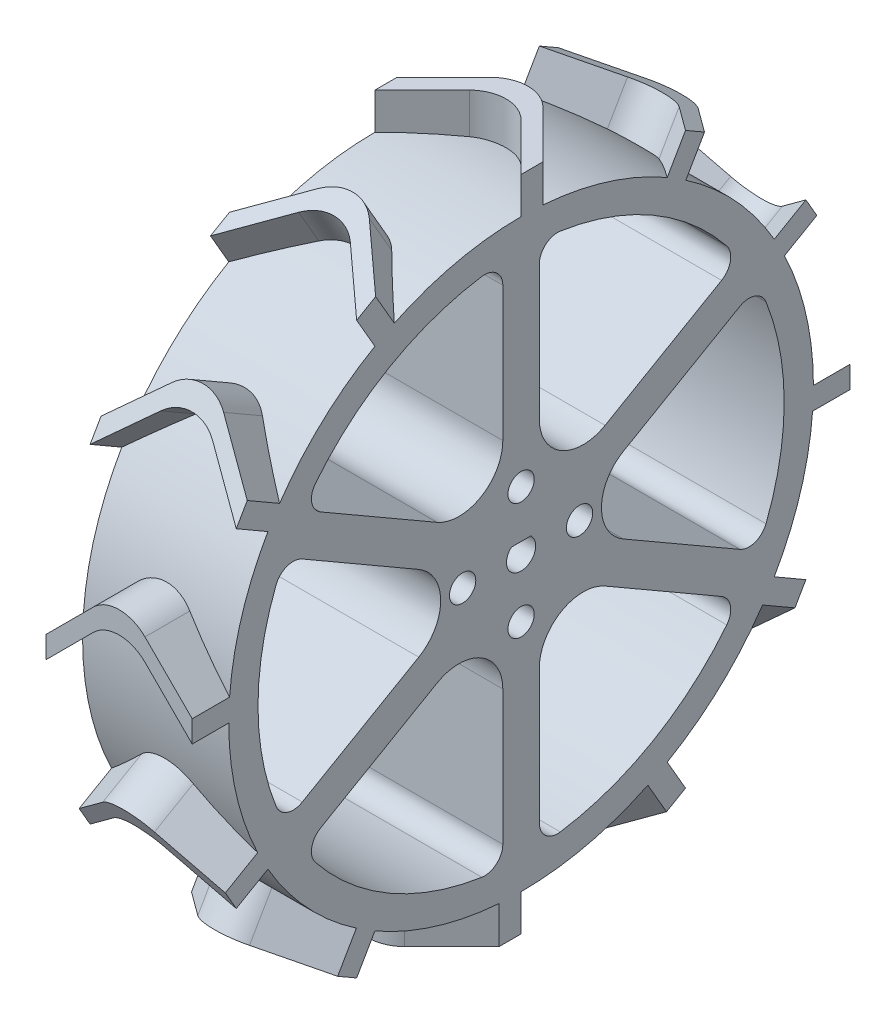
SolidWorks part; units mm, degrees
material "PLA 15%"
ref_plane "Front Plane" through (0, 0, 0) normal (0, 0, 1) x (1, 0, 0)
ref_plane "Top Plane" through (0, 0, 0) normal (0, 1, 0) x (1, 0, 0)
ref_plane "Right Plane" through (0, 0, 0) normal (1, 0, 0) x (0, 0, -1)
sketch "Sketch2" plane through (0, 0, 0) normal (1, 0, 0) x (0, 0, -1)
  circle A2 centre (0, 0) radius 40
  dimension "D1" = 80
extrude "Boss-Extrude1" add sketch "Sketch2" along normal blind 20
sketch "Sketch4" plane through (0, 0, 0) normal (0, 1, 0) x (1, 0, 0)
  line L8 (0, 0) -> (20, 0) construction
  line L9 (20, -40) -> (20, 40) construction
  line L10 (0, 0) -> (6.4645, 6.4645)
  line L11 (13.5355, 6.4645) -> (20, 0)
  line L12 (20, 0) -> (20, 3)
  line L13 (20, 3) -> (13.5355, 9.4645)
  line L14 (6.4645, 9.4645) -> (0, 3)
  line L15 (0, 40) -> (0, -40) construction
  line L16 (0, 3) -> (0, 0)
  arc A0 (13.5355, 9.4645) -> (6.4645, 9.4645) centre (10, 5.9289) ccw
  arc A1 (6.4645, 6.4645) -> (13.5355, 6.4645) centre (10, 2.9289) cw
  point P4 (10, 0)
  point P18 (10, 13)
  point P21 (10, 10)
  dimension "D3" = 5
  dimension "D1" = 3
  dimension "D2" = 3
  dimension "D4" = 10
extrude "Boss-Extrude2" add sketch "Sketch4" along normal blind 45
pattern_circular "CirPattern2" count 12 over 360 about axis through (20, 0, 0) along (-1, 0, 0) of "Boss-Extrude2"
sketch "Sketch5" plane through (0, 0, 0) normal (-1, 0, 0) x (0, 0, 1)
  line L0 (0, 0) -> (0, 40) construction
  line L1 (0, 0) -> (34.641, 20) construction
  line L6 (2.5, 33.1248) -> (2.5, 4.3301)
  line L8 (27.4369, 18.7274) -> (2.5, 4.3301)
  circle A0 centre (0, 0) radius 40 construction
  arc A2 (5.3731, 35.5968) -> (28.1411, 22.4517) centre (0, 0) cw
  arc A6 (28.1411, 22.4517) -> (27.4369, 18.7274) centre (26.1869, 20.8925) cw
  arc A7 (5.3731, 35.5968) -> (2.5, 33.1248) centre (5, 33.1248) ccw
  circle A10 centre (0, 0) radius 40 construction
  point P11 (0, 35.9131)
  point P22 (2.5, 35.9131)
  dimension "D1" = 2.5
  dimension "D2" = 4
  dimension "D8" = 2.5
  dimension "D7" = 2.5
  dimension "D9" = 60
extrude "Cut-Extrude3" cut sketch "Sketch5" against normal up to next
fillet "Fillet1" radius 6 1 edges at (10, 4.3301, 2.5)
pattern_circular "CirPattern3" count 6 over 360 about axis through (0, 0, 0) along (1, 0, 0) of "Cut-Extrude3", "Fillet1"
sketch "Sketch6" plane through (0, 0, 0) normal (-1, 0, 0) x (0, 0, 1)
  circle A0 centre (0, 8) radius 1.8
  circle A1 centre (8, 0) radius 1.8
  circle A2 centre (0, -8) radius 1.8
  circle A3 centre (-8, 0) radius 1.8
  point P0 (0, 0)
  point P13 (0, 0)
  dimension "D1" = 3.6
  dimension "D2" = 8
  dimension "D3" = 4
extrude "Cut-Extrude4" cut sketch "Sketch6" against normal up to next
sketch "Sketch8" plane through (0, 0, 0) normal (1, 0, 0) x (0, 0, -1)
  line L0 (1.3229, 1.5) -> (-1.3229, 1.5)
  arc A0 (1.3229, 1.5) -> (-1.3229, 1.5) centre (0, 0) cw
  point P4 (0, -2)
  dimension "D1" = 2
  dimension "D2" = 3.5
extrude "Cut-Extrude6" cut sketch "Sketch8" along normal through all both and the other way through all contours A0 L0
